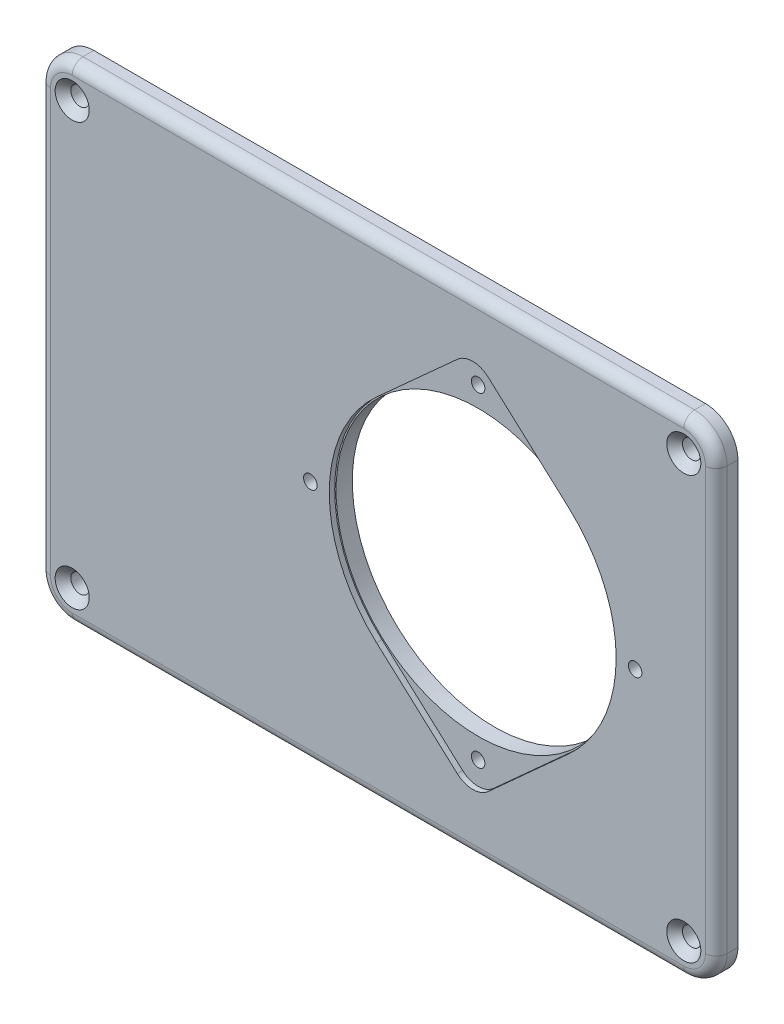
SolidWorks part; units mm, degrees
ref_plane "Front Plane" through (0, 0, 0) normal (0, 0, 1) x (1, 0, 0)
ref_plane "Top Plane" through (0, 0, 0) normal (0, 1, 0) x (1, 0, 0)
ref_plane "Right Plane" through (0, 0, 0) normal (1, 0, 0) x (0, 0, -1)
sketch "Sketch1" plane through (0, 0, 0) normal (0, 0, 1) x (1, 0, 0)
  line L1 (-62.5, 45) -> (62.5, 45)
  line L2 (-62.5, 45) -> (-62.5, -45)
  line L3 (-62.5, -45) -> (62.5, -45)
  line L4 (62.5, 45) -> (62.5, -45)
  line L5 (-62.5, 45) -> (62.5, -45) construction
  line L6 (-62.5, -45) -> (62.5, 45) construction
  point P0 (0, 0)
  dimension "D1" = 90
  dimension "D2" = 125
extrude "Boss-Extrude1" add sketch "Sketch1" along normal blind 4
sketch "Sketch2" plane through (0, 0, 4) normal (0, 0, 1) x (1, 0, 0)
  line L0 (-62.5, 0) -> (62.5, 0) construction
  line L1 (62.5, -45) -> (62.5, 45) construction
  line L6 (17.5, -45) -> (17.5, 45) construction
  line L7 (62.5, 45) -> (-62.5, 45) construction
  line L8 (-0.2754, 19.6542) -> (14.6492, 33.1521)
  line L9 (20.3508, 33.1521) -> (35.2754, 19.6542)
  line L10 (35.2754, -19.6542) -> (20.3508, -33.1521)
  line L11 (-0.2754, -19.6542) -> (14.6492, -33.1521)
  circle A0 centre (17.5, 0) radius 26.25
  arc A7 (-0.2754, 19.6542) -> (-0.2754, -19.6542) centre (17.5, 0) ccw
  arc A8 (20.3508, 33.1521) -> (14.6492, 33.1521) centre (17.5, 30) ccw
  arc A10 (35.2754, -19.6542) -> (35.2754, 19.6542) centre (17.5, 0) ccw
  arc A11 (14.6492, -33.1521) -> (20.3508, -33.1521) centre (17.5, -30) ccw
  point P6 (0, 0)
  point P9 (17.5, 30)
  point P14 (47.5, 0)
  point P16 (-12.5, 0)
  point P24 (17.5, 0)
  point P25 (17.5, -30)
  dimension "D1" = 52.5
  dimension "D3" = 53
  dimension "D4" = 4.25
  dimension "D5" = 4.25
  dimension "D8" = 30
  dimension "D2" = 17.5
  dimension "D6" = 30
  dimension "D7" = 30
  dimension "D9" = 30
extrude "Cut-Extrude2" cut sketch "Sketch2" against normal through all contours A0
fillet "Fillet1" radius 6 4 edges at (-62.5, -45, 2) (62.5, -45, 2) (62.5, 45, 2) (-62.5, 45, 2)
fillet "Fillet2" radius 2 8 edges at (-60.7426, 43.2426, 4) (0, 45, 4) (60.7426, 43.2426, 4) (62.5, 0, 4) (60.7426, -43.2426, 4) (0, -45, 4) (-60.7426, -43.2426, 4) (-62.5, 0, 4)
hole_wizard "CSK for M3 Flat Head Machine Screw1" positions "Sketch7" profile "Sketch8" countersink size "M3" standard "ANSI Metric" end condition through all
sketch "Sketch7" plane through (0, 0, 4) normal (0, 0, 1) x (1, 0, 0)
  point P0 (-56.5, 39)
  point P3 (56.5, 39)
  point P6 (56.5, -39)
  point P9 (-56.5, -39)
sketch "Sketch8" plane through (-56.5, 39, 4) normal (1, 0, 0) x (0, -1, 0)
  line L0 (0, 0) -> (0, 4)
  line L1 (0, 4) -> (1.7, 4)
  line L2 (1.7, 4) -> (1.7, 1.45)
  line L3 (1.7, 1.45) -> (3.15, 0)
  line L5 (3.15, 0) -> (0, 0)
  line L6 (-1.7, 1.45) -> (-3.15, 0) construction
  line L11 (0, -6.35) -> (0, 107.95) construction
  dimension "Thru Hole Dia." = 3.4
  dimension "Thru Hole Depth" = 4
  dimension "Near C'Sink Dia." = 6.3
  dimension "Near C'Sink Angle" = 90
extrude "Cut-Extrude3" cut sketch "Sketch2<5>" against normal blind 1 contours L8 A8 L9 A10 L10 A11 L11 A7
sketch "Sketch2<5>" plane through (0, 0, 4) normal (0, 0, 1) x (1, 0, 0) same geometry as "Sketch2"
hole_wizard "M3x0.5 Tapped Hole1" positions "Sketch9" profile "Sketch10" tap size "M3x0.5" standard "ANSI Metric" end condition through all
sketch "Sketch9" plane through (0, 0, 4) normal (0, 0, 1) x (1, 0, 0)
  point P0 (17.5, 30)
  point P3 (47.5, 0)
  point P6 (17.5, -30)
  point P9 (-12.5, 0)
sketch "Sketch10" plane through (17.5, 30, 4) normal (1, 0, 0) x (0, -1, 0)
  line L0 (0, 0) -> (0, 4)
  line L1 (0, 4) -> (1.25, 4)
  line L2 (1.25, 4) -> (1.25, 0)
  line L5 (1.25, 0) -> (0, 0)
  line L11 (0, -6.35) -> (0, 107.95) construction
  dimension "Thread Major Dia." = 2.5
  dimension "Thru Tap Drill Depth" = 4
